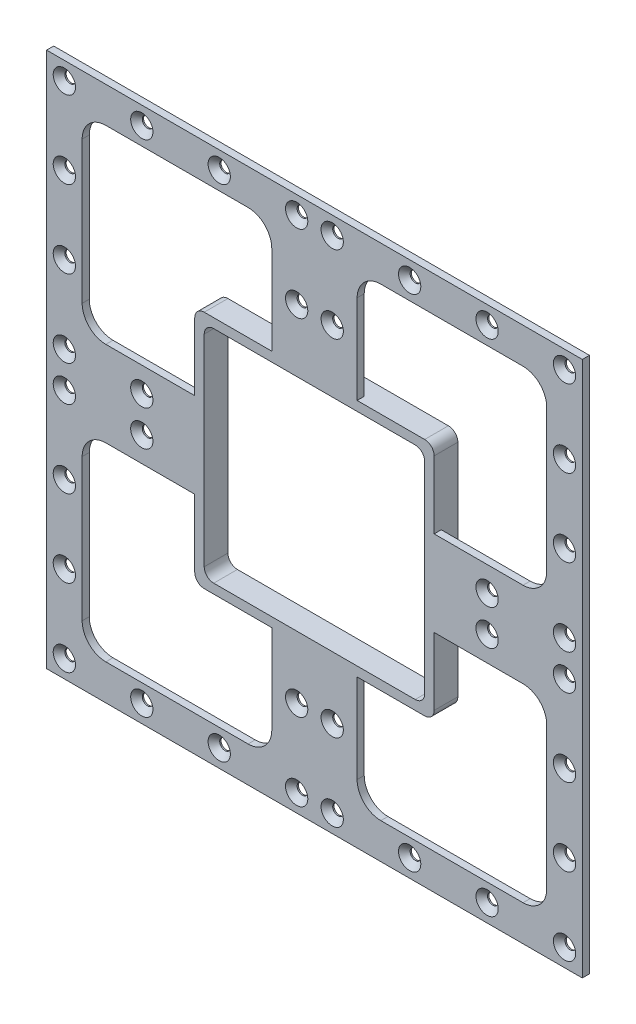
SolidWorks part; units mm, degrees
material "6061-T6 (SS)"
ref_plane "Alzado" through (0, 0, 0) normal (0, 0, 1) x (1, 0, 0)
ref_plane "Planta" through (0, 0, 0) normal (0, 1, 0) x (1, 0, 0)
ref_plane "Vista lateral" through (0, 0, 0) normal (1, 0, 0) x (0, 0, -1)
sketch "Sketch1" plane through (0, 0, 0) normal (0, 0, 1) x (1, 0, 0)
  line L1 (-113, 113) -> (113, 113)
  line L2 (-113, 113) -> (-113, -113)
  line L3 (-113, -113) -> (113, -113)
  line L4 (113, 113) -> (113, -113)
  line L5 (-113, 113) -> (113, -113) construction
  line L6 (-113, -113) -> (113, 113) construction
  point P0 (0, 0)
  dimension "D1" = 226
  dimension "D2" = 226
extrude "Boss-Extrude1" add sketch "Sketch1" along normal blind 3
sketch "Sketch2" plane through (0, 0, 0) normal (0, 0, 1) x (1, 0, 0)
  line L0 (-113, 113) -> (-113, -113) construction
  line L1 (-98, 98) -> (-18, 98)
  line L2 (-98, 98) -> (-98, 18)
  line L3 (-98, 18) -> (-18, 18)
  line L4 (-18, 98) -> (-18, 18)
  line L5 (-98, 98) -> (-18, 18) construction
  line L6 (-98, 18) -> (-18, 98) construction
  line L7 (113, 113) -> (-113, 113) construction
  point P0 (-58, 58)
  point P9 (-58, 98)
  dimension "D1" = 80
  dimension "D2" = 80
  dimension "D3" = 15
  dimension "D4" = 15
extrude "Cut-Extrude2" cut sketch "Sketch2" along normal through all
fillet "Fillet1" radius 10 4 edges at (-98, 98, 1.5) (-18, 98, 1.5) (-18, 18, 1.5) (-98, 18, 1.5)
pattern_linear "LPattern2" count 2 spacing 116 along (0, -1, 0) count 2 spacing 116 along (1, 0, 0) of "Fillet1", "Cut-Extrude2"
sketch "Sketch11" plane through (0, 0, 3) normal (0, 0, 1) x (1, 0, 0)
  line L0 (-113, 113) -> (-113, -113) construction
  line L1 (113, 113) -> (-113, 113) construction
  point P0 (-105.5, 105.5)
  dimension "D1" = 7.5
  dimension "D2" = 7.5
hole_wizard "CSK for M4 Flat Head Machine Screw4" positions "Sketch11" profile "Sketch12" countersink size "M4" standard "ANSI Metric" end condition through all
sketch "Sketch12" plane through (-105.5, 105.5, 3) normal (1, 0, 0) x (0, -1, 0)
  line L0 (0, 0) -> (0, 3)
  line L1 (0, 3) -> (2.25, 3)
  line L2 (2.25, 3) -> (2.25, 2.45)
  line L3 (2.25, 2.45) -> (4.7, 0)
  line L5 (4.7, 0) -> (0, 0)
  line L6 (-2.25, 2.45) -> (-4.7, 0) construction
  line L11 (0, -6.35) -> (0, 107.95) construction
  dimension "Thru Hole Dia." = 4.5
  dimension "Thru Hole Depth" = 3
  dimension "Near C'Sink Dia." = 9.4
  dimension "Near C'Sink Angle" = 90
sketch "Sketch13" plane through (0, 0, 3) normal (0, 0, 1) x (1, 0, 0)
  line L0 (0, 113) -> (0, -113) construction
  line L1 (113, 113) -> (-113, 113) construction
  line L2 (-113, -113) -> (113, -113) construction
  line L3 (-113, 0) -> (113, 0) construction
  line L4 (-113, 113) -> (-113, -113) construction
  line L5 (113, -113) -> (113, 113) construction
pattern_linear "LPattern8" count 4 spacing 32.6667 along (1, 0, 0) count 4 spacing 32.6667 along (0, -1, 0) skipping (1, 1), (1, 2), (2, 1), (2, 2) of "CSK for M4 Flat Head Machine Screw4"
mirror "Mirror1" about plane through (0, 0, 0) normal (1, 0, 0) of "LPattern8" second plane through (0, 0, 0) second plane normal (0, 1, 0)
sketch "Sketch14" plane through (0, 0, 3) normal (0, 0, 1) x (1, 0, 0)
  line L1 (-50.5, 50.5) -> (50.5, 50.5)
  line L2 (-50.5, 50.5) -> (-50.5, -50.5)
  line L3 (-50.5, -50.5) -> (50.5, -50.5)
  line L4 (50.5, 50.5) -> (50.5, -50.5)
  line L5 (-50.5, 50.5) -> (50.5, -50.5) construction
  line L6 (-50.5, -50.5) -> (50.5, 50.5) construction
  point P0 (0, 0)
  dimension "D1" = 101
  dimension "D2" = 101
extrude "Cut-Extrude3" cut sketch "Sketch14" against normal up to next
sketch "Sketch15" plane through (0, 0, 3) normal (0, 0, 1) x (1, 0, 0)
  line L1 (-50.5, 50.5) -> (50.5, 50.5)
  line L2 (-50.5, 50.5) -> (-50.5, -50.5)
  line L3 (-50.5, -50.5) -> (50.5, -50.5)
  line L4 (50.5, 50.5) -> (50.5, -50.5)
  line L5 (-50.5, 50.5) -> (50.5, -50.5) construction
  line L6 (-50.5, -50.5) -> (50.5, 50.5) construction
  line L7 (-46.5, 46.5) -> (46.5, 46.5)
  line L8 (-46.5, 46.5) -> (-46.5, -46.5)
  line L9 (-46.5, -46.5) -> (46.5, -46.5)
  line L10 (46.5, 46.5) -> (46.5, -46.5)
  line L11 (-46.5, 46.5) -> (46.5, -46.5) construction
  line L12 (-46.5, -46.5) -> (46.5, 46.5) construction
  point P0 (0, 0)
  point P6 (0, 0)
  dimension "D1" = 101
  dimension "D2" = 4
extrude "Boss-Extrude2" add sketch "Sketch15" against normal blind 10
fillet "Fillet2" radius 4 8 edges at (-46.5, -46.5, -2) (-50.5, -50.5, -2) (46.5, -46.5, -2) (50.5, -50.5, -2) (46.5, 46.5, -2) (50.5, 50.5, -2) (-46.5, 46.5, -2) (-50.5, 50.5, -2)
